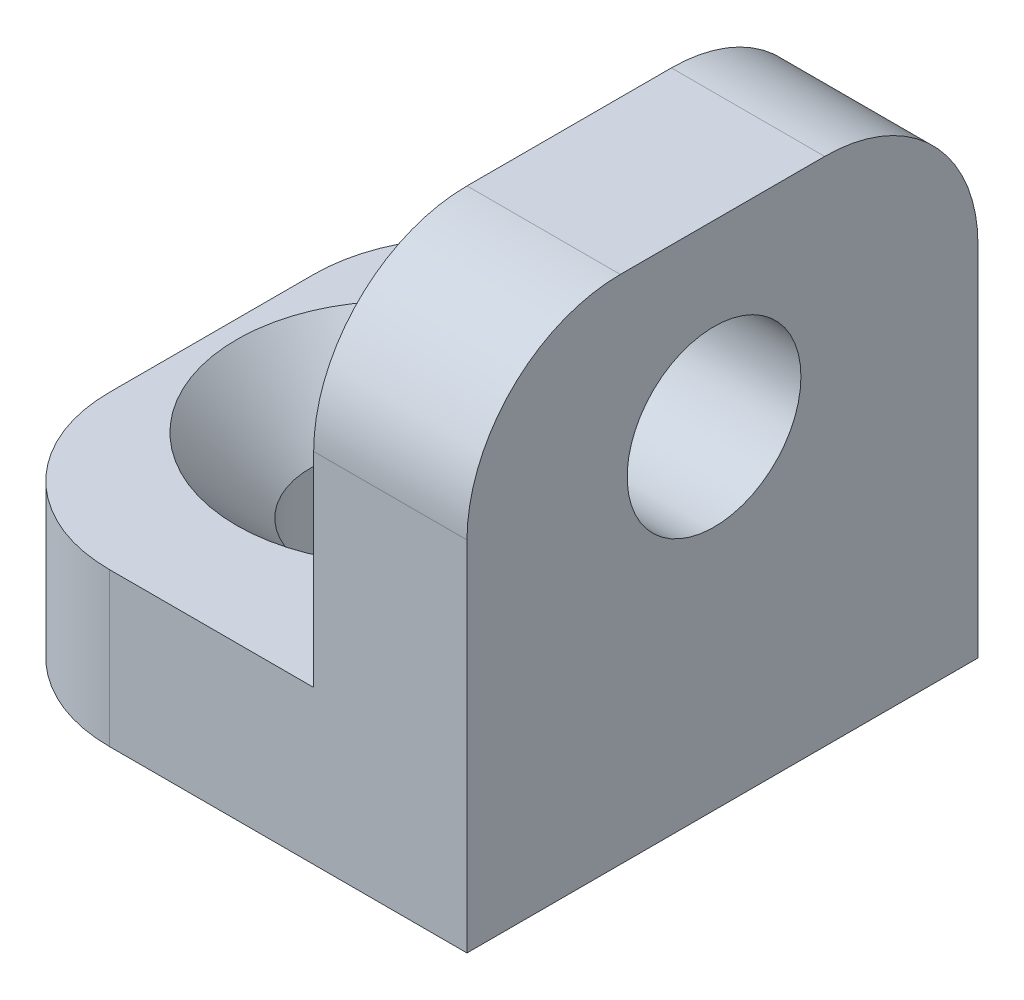
SolidWorks part; units mm, degrees
ref_plane "Plan de face" through (0, 0, 0) normal (0, 0, 1) x (1, 0, 0)
ref_plane "Plan de dessus" through (0, 0, 0) normal (0, 1, 0) x (1, 0, 0)
ref_plane "Plan de droite" through (0, 0, 0) normal (1, 0, 0) x (0, 0, -1)
sketch "Esquisse1" plane through (0, 0, 0) normal (0, 0, 1) x (1, 0, 0)
  line L0 (0, 0) -> (10, 0)
  line L1 (0, 0) -> (10, 0) construction
  line L2 (0, 0) -> (0, 10) construction
  line L3 (0, 10) -> (10, 10) construction
  line L4 (10, 0) -> (10, 10) construction
  line L5 (10, 0) -> (10, 10)
  line L6 (10, 10) -> (7, 10)
  line L7 (7, 10) -> (7, 3)
  line L8 (7, 3) -> (0, 3)
  line L9 (0, 3) -> (0, 0)
  dimension "D1" = 10
  dimension "D2" = 10
  dimension "D3" = 3
  dimension "D4" = 3
extrude "Boss.-Extru.1" add sketch "Esquisse1" along normal blind 10
sketch "Esquisse2" plane through (10, 0, 0) normal (1, 0, 0) x (0, 0, -1)
  line L0 (-10, 10) -> (0, 10) construction
  circle A0 centre (-5.1651, 6.5) radius 1.5
  dimension "D2" = 3
  dimension "D1" = 3.5
extrude "Enlèv. mat.-Extru.1" cut sketch "Esquisse2" against normal up to surface (3 mm away) up to face at (7, 6.5, 5)
sketch "Esquisse3" plane through (0, 3, 0) normal (0, 1, 0) x (1, 0, 0)
  line L0 (0, -10) -> (0, 0) construction
  circle A0 centre (3.5, -4.8584) radius 1.5
  dimension "D2" = 3
  dimension "D1" = 3.5
extrude "Enlèv. mat.-Extru.2" cut sketch "Esquisse3" against normal up to surface (3 mm away) up to face at (5, 0, 5)
hole_wizard "Dégagement M31" positions "Esquisse4" profile "Esquisse5" hole size "M3" standard "ISO"
sketch "Esquisse4" plane through (10, 0, 0) normal (1, 0, 0) x (0, 0, -1)
  point P0 (-5.1651, 6.5)
sketch "Esquisse5" plane through (10, 6.5, 5.1651) normal (0, 1, 0) x (0, 0, -1)
  line L0 (0, 0) -> (0, 4.0215)
  line L1 (0, 4.0215) -> (1.7, 3)
  line L2 (1.7, 3) -> (1.7, 0)
  line L5 (1.7, 0) -> (0, 0)
  line L10 (0, 4.0215) -> (-1.7, 3) construction
  line L11 (0, -6.35) -> (0, 107.95) construction
  dimension "Diamètre du perçage" = 3.4
  dimension "Profondeur du perçage" = 3
  dimension "Angle de pointe" = 118
hole_wizard "Fraisage pour vis à tête fraisée M31" positions "Esquisse6" profile "Esquisse7" countersink size "M3" standard "ISO"
sketch "Esquisse6" plane through (0, 3, 0) normal (0, 1, 0) x (1, 0, 0)
  point P0 (3.5, -4.8584)
sketch "Esquisse7" plane through (3.5, 3, 4.8584) normal (1, 0, 0) x (0, 0, 1)
  line L0 (0, 0) -> (0, 4.0215)
  line L1 (0, 4.0215) -> (1.7, 3)
  line L2 (1.7, 3) -> (1.7, 1.45)
  line L3 (1.7, 1.45) -> (3.15, 0)
  line L5 (3.15, 0) -> (0, 0)
  line L6 (-1.7, 1.45) -> (-3.15, 0) construction
  line L10 (0, 4.0215) -> (-1.7, 3) construction
  line L11 (0, -6.35) -> (0, 107.95) construction
  dimension "Diamètre du perçage" = 3.4
  dimension "Profondeur du perçage" = 3
  dimension "Diamètre du fraisage entrant" = 6.3
  dimension "Angle du fraisage entrant" = 90
  dimension "Angle de pointe" = 118
fillet "Congé1" radius 3 4 edges at (0, 1.5, 10) (0, 1.5, 0) (8.5, 10, 0) (8.5, 10, 10)
